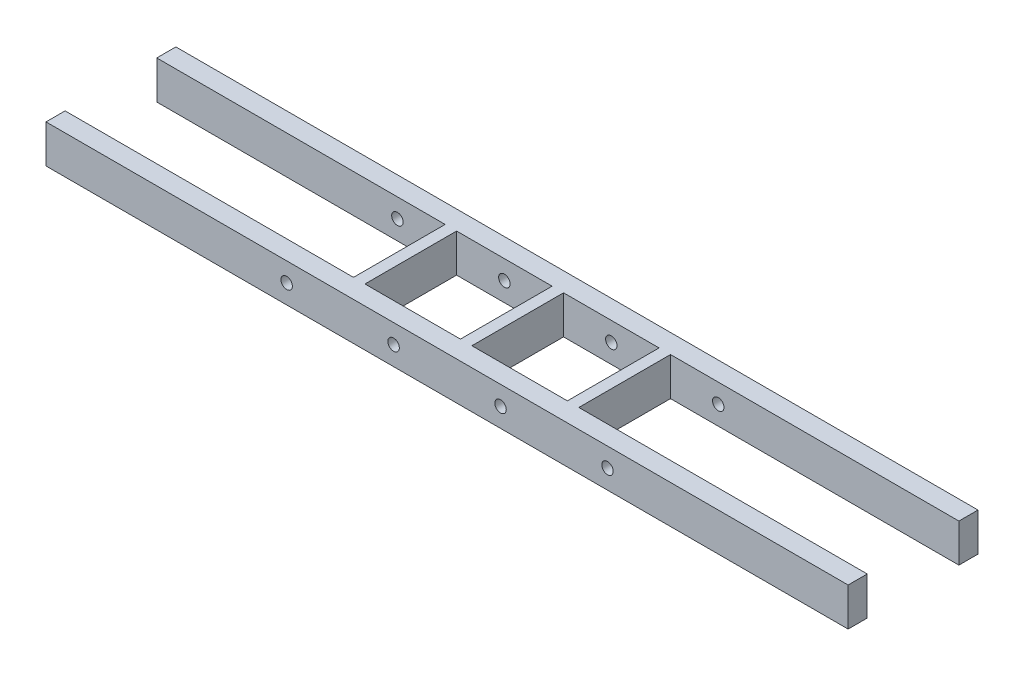
SolidWorks part; units mm, degrees
ref_plane "前视基准面" through (0, 0, 0) normal (0, 0, 1) x (1, 0, 0)
ref_plane "上视基准面" through (0, 0, 0) normal (0, 1, 0) x (1, 0, 0)
ref_plane "右视基准面" through (0, 0, 0) normal (1, 0, 0) x (0, 0, -1)
other "Configuration Table"
sketch "草图1" plane through (0, 0, 0) normal (0, 0, 1) x (1, 0, 0)
  line L0 (-100, 0) -> (100, 0) construction
  line L1 (-105, -5) -> (105, -5)
  line L2 (-105, -5) -> (-105, 5)
  line L3 (-105, 5) -> (105, 5)
  line L4 (105, -5) -> (105, 5)
  line L5 (-105, -5) -> (105, 5) construction
  line L6 (-105, 5) -> (105, -5) construction
  line L7 (0, 24.0554) -> (0, -52.1273) construction
  line L8 (-100, -40.1628) -> (0, -40.1628) construction
  line L9 (0, -40.1628) -> (100, -40.1628) construction
  line L10 (-50, -40.1628) -> (-50, -63.9624) construction
  line L11 (50, -40.1628) -> (50, -63.9624) construction
  line L12 (-50, -58.5361) -> (-100, -58.5361) construction
  line L13 (-50, -58.5361) -> (0, -58.5361) construction
  line L14 (0, -58.5361) -> (50, -58.5361) construction
  line L15 (50, -58.5361) -> (100, -58.5361) construction
  line L16 (-75, -58.5361) -> (-75, -63.9624) construction
  line L17 (-25, -58.5361) -> (-25, -63.9624) construction
  line L18 (25, -58.5361) -> (25, -63.9624) construction
  line L19 (75, -58.5361) -> (75, -63.9624) construction
  line L21 (-42, 0) -> (-14, 0)
  line L22 (-14, 0) -> (14, 0)
  line L24 (14, 0) -> (42, 0)
  line L32 (-29.5, -5) -> (-26.5, -5)
  line L33 (-29.5, -5) -> (-29.5, 5)
  line L34 (-29.5, 5) -> (-26.5, 5)
  line L35 (-26.5, -5) -> (-26.5, 5)
  line L36 (-29.5, -5) -> (-26.5, 5) construction
  line L37 (-29.5, 5) -> (-26.5, -5) construction
  line L38 (-1.5, -5) -> (1.5, -5)
  line L39 (-1.5, -5) -> (-1.5, 5)
  line L40 (-1.5, 5) -> (1.5, 5)
  line L41 (1.5, -5) -> (1.5, 5)
  line L42 (-1.5, -5) -> (1.5, 5) construction
  line L43 (-1.5, 5) -> (1.5, -5) construction
  line L44 (26.5, -5) -> (29.5, -5)
  line L45 (26.5, -5) -> (26.5, 5)
  line L46 (26.5, 5) -> (29.5, 5)
  line L47 (29.5, -5) -> (29.5, 5)
  line L48 (26.5, -5) -> (29.5, 5) construction
  line L49 (26.5, 5) -> (29.5, -5) construction
  circle A1 centre (-42, 0) radius 1.5
  circle A2 centre (-14, 0) radius 1.5
  circle A3 centre (14, 0) radius 1.5
  circle A4 centre (42, 0) radius 1.5
  point P0 (0, 0)
  point P30 (-32.5583, -8.8441)
  point P31 (0, 0)
  point P40 (0, 0)
  point P41 (0, 0)
  point P43 (5.0599, -11.7737)
  point P44 (0, 0)
  point P45 (-27.378, 0)
  point P47 (-28, 0)
  point P57 (28, 0)
  dimension "D4" = 3
  dimension "D1" = 200
  dimension "D2" = 5
  dimension "D3" = 10
  dimension "D5" = 14
  dimension "D6" = 14
  dimension "D7" = 3
extrude "凸台-拉伸1" add sketch "草图1" along normal blind 5 contours L3 L4 L1 L2 | A1 | A2 | A3 | A4
ref_plane "基准面1" through (0, 0, 29) normal (0, 0, 1) x (1, 0, 0)
extrude "凸台-拉伸2" add sketch "草图1<3>" along normal blind 5 from surface separate body contours L3 L4 L1 L2 | A3 | A2 | A1 | A4 starting at plane "基准面1"
sketch "草图1<3>" plane through (0, 0, 0) normal (0, 0, 1) x (1, 0, 0) same geometry as "草图1"
extrude "凸台-拉伸3" add sketch "草图1<4>" along normal up to surface (29 mm away) contours L33 L34 L35 L32 | L39 L40 L41 L38 | L45 L46 L47 L44 up to face at (-40.5, 0, 29)
sketch "草图1<4>" plane through (0, 0, 0) normal (0, 0, 1) x (1, 0, 0) same geometry as "草图1"
